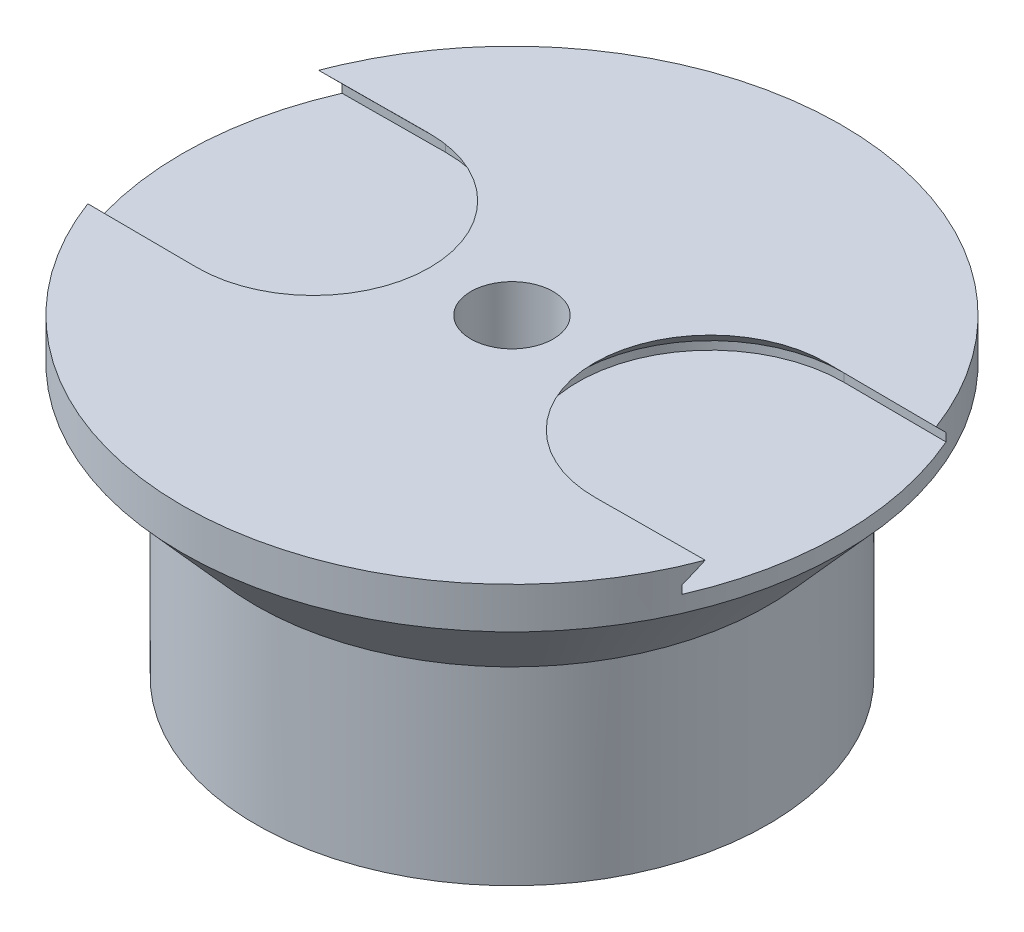
SolidWorks part; units mm, degrees
ref_plane "Front Plane" through (0, 0, 0) normal (0, 0, 1) x (1, 0, 0)
ref_plane "Top Plane" through (0, 0, 0) normal (0, 1, 0) x (1, 0, 0)
ref_plane "Right Plane" through (0, 0, 0) normal (1, 0, 0) x (0, 0, -1)
sketch "Sketch1" plane through (0, 0, 0) normal (0, 1, 0) x (1, 0, 0)
  circle A0 centre (0, 0) radius 31.06
  circle A1 centre (0, 0) radius 5
  dimension "D1" = 62.12
  dimension "D2" = 10
extrude "Boss-Extrude1" add sketch "Sketch1" along normal blind 35
sketch "Sketch18" plane through (0, 0, 0) normal (0, -1, 0) x (1, 0, 0)
  circle A0 centre (0, 0) radius 7.5
  circle A1 centre (0, 0) radius 28.66
  circle A2 centre (0, 0) radius 31.06 construction
  circle A3 centre (0, 0) radius 5 construction
  dimension "D1" = 2.4
  dimension "D2" = 2.5
extrude "Cut-Extrude12" cut sketch "Sketch18" against normal blind 13
sketch "Sketch19" plane through (0, 0, 0) normal (0, -1, 0) x (1, 0, 0)
  circle A0 centre (0, 0) radius 7.5 construction
  circle A1 centre (0, 0) radius 7.5
curve "Helix/Spiral1" pitch 12 height 12 radius 7.5 centre (0, 0, 0) axis (0, 1, 0) start towards (0, 0, -1)
sketch "Sketch20" plane through (0, 0, 0) normal (1, 0, 0) x (0, 0, -1)
  line L1 (-7.5, 0) -> (7.5, 0) construction
  line L2 (7.5, -0.6294) -> (7.5, 0.6294)
  line L4 (7.5, 0.6294) -> (8.5, 0.3457)
  line L5 (8.5, 0.3457) -> (8.5, -0.3956)
  line L6 (8.5, -0.3956) -> (7.5, -0.6294)
  line L7 (8, -0.5125) -> (8, 0.4875)
  line L8 (-7.5, 0) -> (7.5, 0)
  dimension "D1" = 1
  dimension "D2" = 29
  dimension "D3" = 1
sweep "Sweep2" add profiles "Sketch20" path "Helix/Spiral1"
pattern_circular "CirPattern8" count 4 over 360 about axis through (0, 0, 0) along (0, -1, 0) of "Sweep2"
sketch "Sketch24" plane through (0, 0, 0) normal (0, 0, 1) x (1, 0, 0)
  line L1 (-31.06, 0) -> (31.06, 0) construction
  line L2 (-31.06, 0) -> (-28.66, 0)
  line L3 (-31.06, 0) -> (-28.66, 2.4)
  line L5 (-28.66, 0) -> (-28.66, 2.4)
  line L6 (28.66, 0) -> (31.06, 0)
  dimension "D1" = 45
ref_axis "Axis1" through (0, 35, 0) along (0, -1, 0)
revolve "Cut-Revolve1" cut sketch "Sketch24" angle 360 about axis through (0, 35, 0) along (0, -1, 0)
sketch "Sketch25" plane through (0, 35, 0) normal (0, 1, 0) x (1, 0, 0)
sketch "Sketch28" plane through (0, 13, 0) normal (0, -1, 0) x (1, 0, 0)
  circle A0 centre (0, 0) radius 7.5 construction
  circle A1 centre (0, 0) radius 28.66
  circle A2 centre (0, 0) radius 28.66
  circle A3 centre (0, 0) radius 7.5
  dimension "D1" = 0
extrude "Cut-Extrude14" cut sketch "Sketch28" against normal blind 17 draft 32
sketch "Sketch30" plane through (0, 35, 0) normal (0, 1, 0) x (1, 0, 0)
  circle A0 centre (0, 0) radius 5 construction
  circle A2 centre (0, 0) radius 40
  circle A3 centre (0, 0) radius 5
  dimension "D1" = 80
extrude "Boss-Extrude2" add sketch "Sketch30" along normal blind 5
sketch "Sketch31" plane through (0, 40, 0) normal (0, 1, 0) x (1, 0, 0)
  line L0 (40, 0) -> (-40, 0)
  line L1 (40, 13.3) -> (40, -13.3)
  line L2 (40, -13.3) -> (24.1845, -13.3997)
  line L3 (40, 13.3) -> (16.7999, 13.4463)
  line L4 (0, -40) -> (0, 40)
  line L5 (-40, 13.3) -> (-16.7999, 13.4463)
  line L6 (-40, -13.3) -> (-24.1845, -13.3997)
  line L7 (-40, 13.3) -> (-40, -13.3)
  circle A0 centre (0, 0) radius 40 construction
  circle A1 centre (24.1, 0) radius 13.4
  circle A2 centre (-24.1, 0) radius 13.4
  circle M2 centre (0, 0) radius 40
  dimension "D1" = 26.8
  dimension "D2" = 26.6
  dimension "D3" = 15.9
extrude "Cut-Extrude16" cut sketch "Sketch31" against normal blind 1 from offset 2 contours A2 L0 | A2 L0 | L0 A2 L5 M2 | L6 A2 L0 M2 | A1 L0 | L0 A1 | A1 L2 L0 M2 | A1 L0 L3 M2 | A1 region at (36.0401, 40, 8.4076) region at (36.0401, 40, -8.4076) region at (24.1, 40, 5.6871) region at (24.1, 40, -5.6871) region at (-36.0401, 40, -8.4076) region at (-36.0401, 40, 8.4076) region at (-24.1, 40, 5.6871) region at (-24.1, 40, -5.6871) offset against normal yes
sketch "Sketch32" plane through (0, 40, 0) normal (0, 1, 0) x (1, 0, 0)
  line L0 (37.7191, 13.3144) -> (37.7191, -13.3144)
  line L1 (0, -40) -> (0, 40) construction
  line L2 (37.7191, 13.3144) -> (24.1845, 13.3997)
  line L3 (24.1845, -13.3997) -> (37.7191, -13.3144)
  line L4 (37.7191, 13.3144) -> (24.1845, 13.3997)
  line L5 (24.1845, -13.3997) -> (37.7191, -13.3144)
  line L6 (-24.1845, 13.3997) -> (-37.7191, 13.3144)
  line L7 (-37.7191, -13.3144) -> (-24.1845, -13.3997)
  line L8 (0, -40) -> (0, 40)
  line L9 (-24.1, -12) -> (-38.1576, -12)
  line L10 (31.06, 0) -> (24.1, 0)
  line L11 (-24.1, 12) -> (-38.1576, 12)
  line L12 (-31.06, 0) -> (-24.1, 0)
  line L13 (-24.1845, -13.3997) -> (-37.7191, -13.3144)
  line L14 (24.1, 12) -> (38.1576, 12)
  line L15 (24.1, -12) -> (38.1576, -12)
  line L16 (-37.7191, 13.3144) -> (-24.1845, 13.3997)
  line L17 (-37.7191, 13.3144) -> (-37.7191, -13.3144)
  circle A0 centre (24.1, 0) radius 12
  arc A1 (-24.1845, 13.3997) -> (-24.1845, -13.3997) centre (-24.1, 0) cw
  arc A2 (24.1845, 13.3997) -> (24.1845, -13.3997) centre (24.1, 0) ccw
  arc A3 (37.7191, -13.3144) -> (37.7191, 13.3144) centre (0, 0) ccw
  arc A4 (24.1845, 13.3997) -> (24.1845, -13.3997) centre (24.1, 0) ccw
  arc A5 (-37.7191, -13.3144) -> (37.7191, 13.3144) centre (0, 0) ccw
  arc A6 (-24.1845, -13.3997) -> (-24.1845, 13.3997) centre (-24.1, 0) ccw
  arc A7 (-37.7191, 13.3144) -> (-37.7191, -13.3144) centre (0, 0) ccw
  circle A8 centre (-24.1, 0) radius 12
  arc A9 (37.7191, 13.3144) -> (-37.7191, -13.3144) centre (0, 0) ccw
  circle M9 centre (0, 0) radius 40
  dimension "D4" = 24
  dimension "D1" = 0
  dimension "D2" = 0
extrude "Cut-Extrude17" cut sketch "Sketch32" against normal up to next contours A8 | L9 A8 L11 L17 | L17 L11 L9 M9 | A0 | A0 L15 L0 L14 | L0 L15 L14 M9 region at (38.6449, 40, 0) region at (37.4431, 40, 0) region at (32.3453, 40, -8.2453) region at (-38.6449, 40, 0) region at (-30.9095, 40, -11.7241) region at (-15.8547, 40, -8.2453)
ref_plane "Plane2" through (40, 0, 0) normal (1, 0, 0) x (0, 0, -1)
sketch "Sketch33" plane through (0, 37, 0) normal (0, 1, 0) x (1, 0, 0)
  line L0 (0, -40) -> (0, 40) construction
  line L1 (0, -40) -> (0, 40)
  line L2 (24.1845, -13.3997) -> (37.7191, -13.3144)
  line L3 (37.7191, 13.3144) -> (24.1845, 13.3997)
  line L4 (24.1845, -13.3997) -> (40, -13.3)
  line L5 (40, 13.3) -> (24.1845, 13.3997)
  line L6 (40, -40) -> (40, 40)
  line L7 (-40, -40) -> (-40, 40)
  line L8 (-40, 13.3) -> (-24.1845, 13.3997)
  line L9 (-24.1845, -13.3997) -> (-40, -13.3)
  arc A0 (-37.7191, -13.3144) -> (-37.7191, 13.3144) centre (0, 0) cw
  arc A1 (-24.1845, 13.3997) -> (-24.1845, -13.3997) centre (-24.1, 0) cw
  arc A2 (24.1845, 13.3997) -> (24.1845, -13.3997) centre (24.1, 0) ccw
  arc A3 (37.7191, -13.3144) -> (37.7191, 13.3144) centre (0, 0) ccw
  arc A4 (24.1845, 13.3997) -> (24.1845, -13.3997) centre (24.1, 0) ccw
  arc A5 (37.7191, -13.3144) -> (37.7191, 13.3144) centre (0, 0) ccw
  dimension "D1" = 0
  dimension "D2" = 40
sketch "Sketch34" plane through (40, 0, 0) normal (1, 0, 0) x (0, 0, -1)
  line L0 (-40, 37) -> (40, 37) construction
  line L1 (-40, 37) -> (40, 37)
  line L2 (-13.3997, 37) -> (-13.3, 37) construction
  line L3 (-13.3997, 37) -> (-13.3, 37)
  line L4 (-13.3, 37) -> (-16, 37)
  line L5 (-16, 37) -> (-16, 38)
  line L6 (-16, 38) -> (-13.3, 40.7)
  line L7 (-13.3, 40.7) -> (-13.3, 37)
  line L8 (-13.3144, 37) -> (-13.3144, 38) construction
  dimension "D1" = 2.7
  dimension "D2" = 45
sweep "Cut-Sweep1" cut profiles "Sketch34" path "Sketch33"
sketch "Sketch35" plane through (0, 40, 0) normal (0, 1, 0) x (1, 0, 0)
  line L4 (37.7191, 13.3144) -> (24.1845, 13.3997)
  line L5 (24.1845, -13.3997) -> (37.7191, -13.3144)
  line L6 (38.1576, -12) -> (24.1, -12)
  line L7 (24.1, 12) -> (38.1576, 12)
  line L8 (37.7191, 13.3144) -> (24.1845, 13.3997)
  line L9 (24.1845, -13.3997) -> (37.7191, -13.3144)
  line L10 (38.1576, -12) -> (24.1, -12)
  line L11 (24.1, 12) -> (38.1576, 12)
  arc A4 (24.1845, 13.3997) -> (24.1845, -13.3997) centre (24.1, 0) ccw
  arc A5 (37.7191, -13.3144) -> (38.1576, -12) centre (0, 0) ccw
  arc A6 (24.1, 12) -> (24.1, -12) centre (24.1, 0) ccw
  arc A7 (38.1576, 12) -> (37.7191, 13.3144) centre (0, 0) ccw
  arc A8 (24.1845, 13.3997) -> (24.1845, -13.3997) centre (24.1, 0) ccw
  arc A9 (37.7191, -13.3144) -> (38.1576, -12) centre (0, 0) ccw
  arc A10 (24.1, 12) -> (24.1, -12) centre (24.1, 0) ccw
  arc A11 (38.1576, 12) -> (37.7191, 13.3144) centre (0, 0) ccw
  dimension "D1" = 0
extrude "Cut-Extrude19" cut sketch "Sketch35" against normal blind 2
ref_plane "Plane3" through (-40, 0, 0) normal (-1, 0, 0) x (0, 0, 1)
sketch "Sketch37" plane through (-40, 0, 0) normal (-1, 0, 0) x (0, 0, 1)
  line L0 (40, 37) -> (-40, 37) construction
  line L1 (40, 37) -> (-40, 37)
  line L2 (-13.3, 37) -> (-13.3997, 37) construction
  line L3 (-13.3, 37) -> (-13.3997, 37)
  line L4 (-13.3, 37) -> (-16, 37)
  line L5 (-16, 37) -> (-16, 38)
  line L6 (-16, 38) -> (-13.3, 40.7)
  line L7 (-13.3, 40.7) -> (-13.3, 37)
  line L8 (-13.3144, 37) -> (-13.3144, 38) construction
  dimension "D1" = 45
  dimension "D2" = 2.7
sweep "Cut-Sweep2" cut profiles "Sketch37" path "Sketch33<3>"
sketch "Sketch33<3>" plane through (0, 37, 0) normal (0, 1, 0) x (1, 0, 0) same geometry as "Sketch33"
sketch "Sketch38" plane through (0, 40, 0) normal (0, 1, 0) x (1, 0, 0)
  line L4 (-37.7191, -13.3144) -> (-24.1845, -13.3997)
  line L5 (-24.1845, 13.3997) -> (-37.7191, 13.3144)
  line L6 (-38.1576, 12) -> (-24.1, 12)
  line L7 (-24.1, -12) -> (-38.1576, -12)
  line L8 (-37.7191, -13.3144) -> (-24.1845, -13.3997)
  line L9 (-24.1845, 13.3997) -> (-37.7191, 13.3144)
  line L10 (-38.1576, 12) -> (-24.1, 12)
  line L11 (-24.1, -12) -> (-38.1576, -12)
  arc A4 (-24.1845, -13.3997) -> (-24.1845, 13.3997) centre (-24.1, 0) ccw
  arc A5 (-37.7191, 13.3144) -> (-38.1576, 12) centre (0, 0) ccw
  arc A6 (-24.1, -12) -> (-24.1, 12) centre (-24.1, 0) ccw
  arc A7 (-38.1576, -12) -> (-37.7191, -13.3144) centre (0, 0) ccw
  arc A8 (-24.1845, -13.3997) -> (-24.1845, 13.3997) centre (-24.1, 0) ccw
  arc A9 (-37.7191, 13.3144) -> (-38.1576, 12) centre (0, 0) ccw
  arc A10 (-24.1, -12) -> (-24.1, 12) centre (-24.1, 0) ccw
  arc A11 (-38.1576, -12) -> (-37.7191, -13.3144) centre (0, 0) ccw
  dimension "D1" = 0
extrude "Cut-Extrude20" cut sketch "Sketch38" against normal blind 2
ref_plane "Plane4" through (0, 25, 0) normal (0, 1, 0) x (1, 0, 0)
sketch "Sketch39" plane through (0, 25, 0) normal (0, 1, 0) x (1, 0, 0)
  circle A1 centre (0, 0) radius 31.06 construction
  circle A2 centre (0, 0) radius 31.06
sketch "Sketch40" plane through (0, 0, 0) normal (0, 0, 1) x (1, 0, 0)
  line L0 (-40, 35) -> (40, 35) construction
  line L1 (-40, 35) -> (40, 35)
  line L2 (31.06, 25) -> (-31.06, 25) construction
  line L3 (31.06, 25) -> (-31.06, 25)
  line L4 (-31.06, 25) -> (-40, 35)
  line L5 (-31.06, 25) -> (-31.06, 35)
  line L6 (-31.06, 35) -> (-31.06, 0) construction
  line L7 (-31.06, 35) -> (-40, 35)
revolve "Revolve1" add sketch "Sketch40" angle 360 about axis through (0, 35, 0) along (0, -1, 0) region at (-34.04, 31.6667, 0)
sketch "Sketch41" plane through (0, 0, 0) normal (0, -1, 0) x (1, 0, 0)
  circle A0 centre (0, 0) radius 10
  dimension "D1" = 20
extrude "Cut-Extrude21" cut sketch "Sketch41" along normal blind 10
sketch "Sketch42" plane through (0, 0, 0) normal (0, -1, 0) x (1, 0, 0)
  circle A1 centre (0, 0) radius 31.06
extrude "Cut-Extrude22" cut sketch "Sketch42" against normal blind 2
